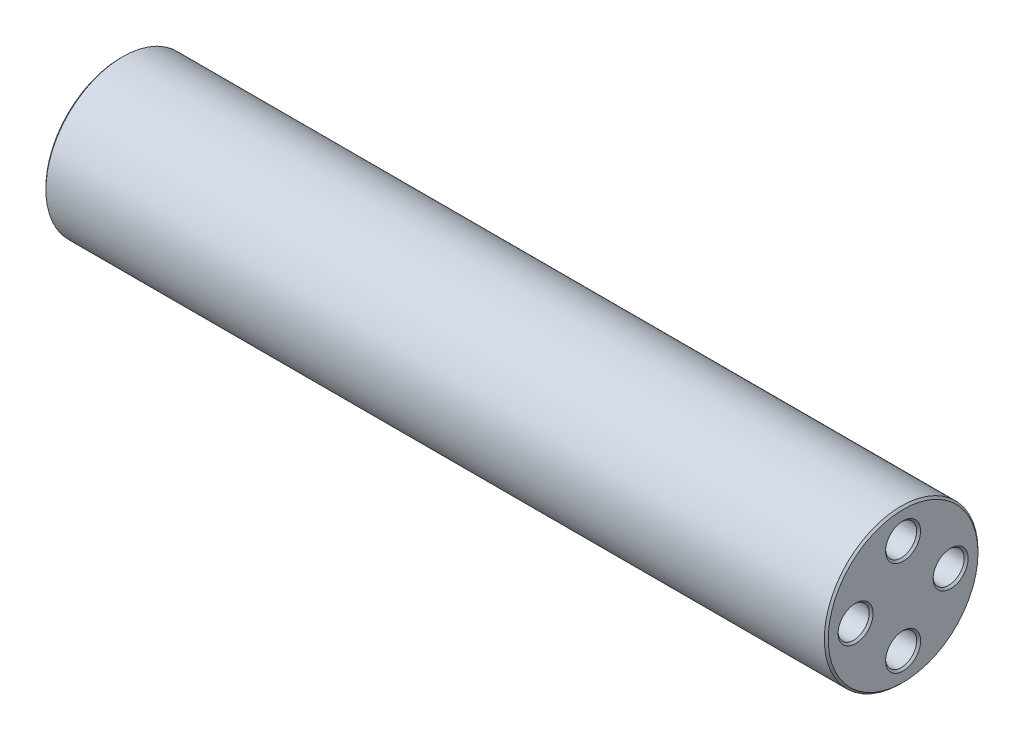
SolidWorks part; units mm, degrees
material "6061-T6 (SS)"
ref_plane "Front Plane" through (0, 0, 0) normal (0, 0, 1) x (1, 0, 0)
ref_plane "Top Plane" through (0, 0, 0) normal (0, 1, 0) x (1, 0, 0)
ref_plane "Right Plane" through (0, 0, 0) normal (1, 0, 0) x (0, 0, -1)
sketch "Sketch2" plane through (0, 0, 0) normal (1, 0, 0) x (0, 0, -1)
  circle A0 centre (0, 0) radius 9.9809
  dimension "D1" = 19.9619
extrude "Boss-Extrude1" add sketch "Sketch2" along normal mid plane 101.6
hole_wizard "#10-32 Tapped Hole1" positions "3DSketch1" profile "Sketch3" tap size "#10-32" standard "ANSI Inch"
sketch3d "3DSketch1"
  line L1 (50.8, 0, 9.9809) -> (50.8, 0, -9.9809) construction
  line L4 (50.8, 9.9809, 0) -> (50.8, -9.9809, 0) construction
  circle A0 centre (50.8, 0, 0) radius 9.9809 construction
  point P0 (50.8, 0, 6.1709)
  point P4 (-50.8, 6.1709, 0)
  point P12 (60.7809, 0, 0)
  point P35 (50.8, -6.1709, 0)
  point P37 (50.8, 0, -6.1709)
  point P39 (50.8, 6.1709, 0)
  point P45 (50.8, 0, 0)
  point P48 (-50.8, 0, 6.1709)
  point P50 (-50.8, -6.1709, 0)
  point P52 (-50.8, 0, -6.1709)
  dimension "D2" = 3.81
  dimension "D1" = 3.81
  dimension "D3" = 3.81
  dimension "D4" = 3.81
sketch "Sketch3" plane through (50.8, 0, 6.1709) normal (0, 1, 0) x (0, 0, -1)
  line L0 (0, 0) -> (0, 13.1513)
  line L1 (0, 13.1513) -> (2.0193, 11.938)
  line L2 (2.0193, 11.938) -> (2.0193, 0)
  line L5 (2.0193, 0) -> (0, 0)
  line L10 (0, 13.1513) -> (-2.0193, 11.938) construction
  line L11 (0, -6.35) -> (0, 107.95) construction
  dimension "Tap Drill Dia." = 4.0386
  dimension "Tap Drill Depth" = 11.938
  dimension "Drill Angle" = 118
cosmetic thread "Hole Thread1" parameters "D1"=9.652, "D2"=4.826
cosmetic thread "Hole Thread2" parameters "D1"=9.652, "D2"=4.826
cosmetic thread "Hole Thread3" parameters "D1"=9.652, "D2"=4.826
cosmetic thread "Hole Thread4" parameters "D1"=9.652, "D2"=4.826
cosmetic thread "Hole Thread5" parameters "D1"=9.652, "D2"=4.826
cosmetic thread "Hole Thread6" parameters "D1"=9.652, "D2"=4.826
cosmetic thread "Hole Thread7" parameters "D1"=9.652, "D2"=4.826
cosmetic thread "Hole Thread8" parameters "D1"=9.652, "D2"=4.826
chamfer "Chamfer1" distance 0.254 angle 45 10 edges at (50.8, 0, -9.9809) (50.8, 0, 4.1516) (-50.8, 0, -9.9809) (-50.8, 6.1709, 2.0193) (50.8, 6.1709, -2.0193) (50.8, 0, -8.1902) (50.8, -6.1709, -2.0193) (-50.8, 0, -4.1516) (-50.8, -6.1709, 2.0193) (-50.8, 0, 8.1902)
equation "\"D1@Sketch2\"=20mm-0.0015"
equation "\"D2@3DSketch1\"=\"D3@3DSketch1\""
equation "\"D1@3DSketch1\"=\"D3@3DSketch1\""
equation "\"D4@3DSketch1\"=\"D3@3DSketch1\""
